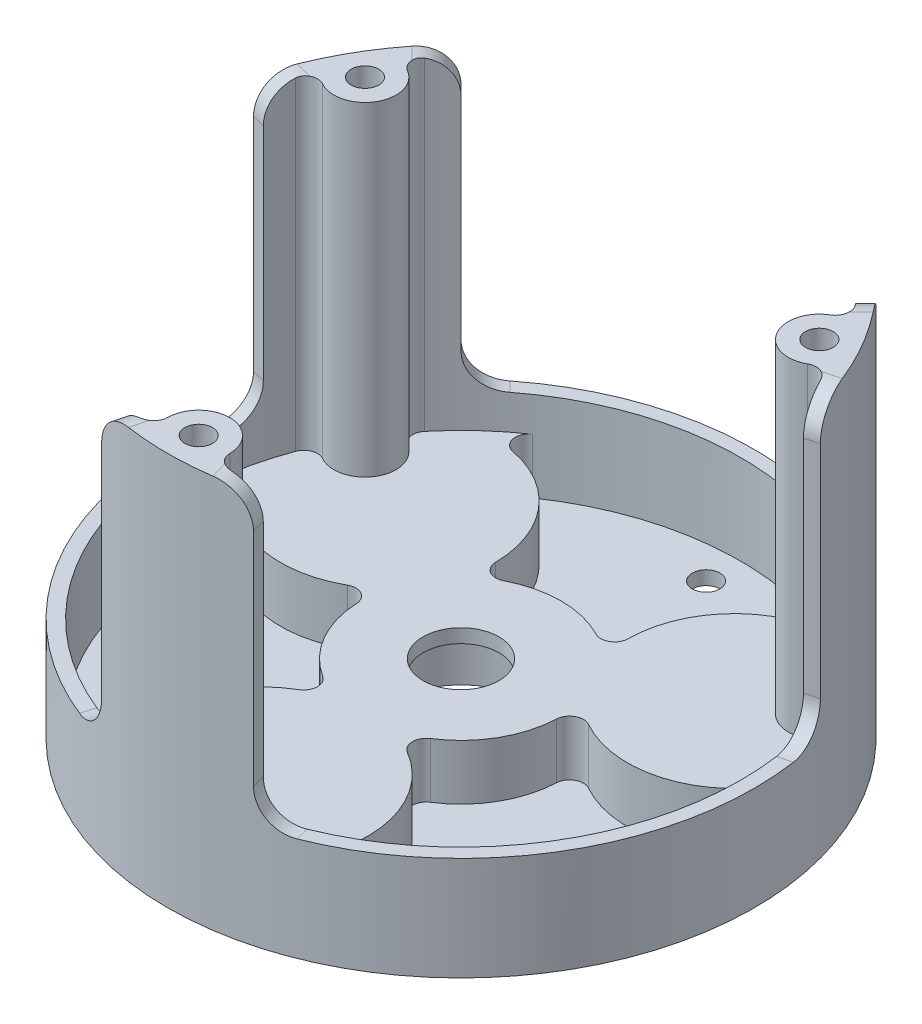
SolidWorks part; units mm, degrees
ref_plane "Front Plane" through (0, 0, 0) normal (0, 0, 1) x (1, 0, 0)
ref_plane "Top Plane" through (0, 0, 0) normal (0, 1, 0) x (1, 0, 0)
ref_plane "Right Plane" through (0, 0, 0) normal (1, 0, 0) x (0, 0, -1)
sketch "Sketch1" plane through (0, 0, 0) normal (0, 1, 0) x (1, 0, 0)
  circle A1 centre (0, 0) radius 42.5
  dimension "D2" = 85
extrude "Boss-Extrude1" add sketch "Sketch1" along normal mid plane 2
sketch "Sketch7" plane through (0, 0, 0) normal (0, 1, 0) x (1, 0, 0)
  circle A0 centre (0, 0) radius 42.5 construction
  arc A1 (-9.2002, -41.4922) -> (9.2002, -41.4922) centre (0, 0) ccw
  arc A3 (-40.5334, 12.7785) -> (-14.0359, 3.6391) centre (-25.1147, 14.5) ccw
  arc A4 (31.3332, 28.7137) -> (10.1695, 10.3359) centre (25.1147, 14.5) ccw
  arc A5 (9.2002, -41.4922) -> (3.8664, -13.975) centre (0, -29) ccw
  arc A6 (-10.1695, 10.3359) -> (-31.3332, 28.7137) centre (-25.1147, 14.5) ccw
  arc A8 (-31.3332, 28.7137) -> (-40.5334, 12.7785) centre (0, 0) ccw
  arc A9 (-14.0359, 3.6391) -> (-3.8664, -13.975) centre (0, 0) ccw
  arc A11 (40.5334, 12.7785) -> (31.3332, 28.7137) centre (0, 0) ccw
  arc A12 (14.0359, 3.6391) -> (40.5334, 12.7785) centre (25.1147, 14.5) ccw
  arc A15 (-3.8664, -13.975) -> (-9.2002, -41.4922) centre (0, -29) ccw
  arc A35 (10.1695, 10.3359) -> (-10.1695, 10.3359) centre (0, 0) ccw
  arc A37 (3.8664, -13.975) -> (14.0359, 3.6391) centre (0, 0) ccw
extrude "Boss-Extrude2" add sketch "Sketch7" along normal blind 9
sketch "Sketch8" plane through (0, 1, 0) normal (0, 1, 0) x (1, 0, 0)
  circle A1 centre (0, 0) radius 42.5
  circle A2 centre (0, 0) radius 40.5
  dimension "D1" = 2
extrude "Boss-Extrude3" add sketch "Sketch8" along normal blind 55
sketch "Sketch11" plane through (0, 9, 0) normal (0, 1, 0) x (1, 0, 0)
  circle A0 centre (-25.1147, 14.5) radius 5
  circle A1 centre (0, -29) radius 5
  circle A2 centre (25.1147, 14.5) radius 5
  dimension "D1" = 10
extrude "Cut-Extrude4" cut sketch "Sketch11" against normal blind 10 from offset 2 offset against normal yes
sketch "Sketch3" plane through (0, -1, 0) normal (0, -1, 0) x (1, 0, 0)
  circle A0 centre (0, 0) radius 9.5
  dimension "D1" = 19
extrude "Cut-Extrude2" cut sketch "Sketch3" against normal blind 8
sketch "Sketch14" plane through (0, 1, 0) normal (0, 1, 0) x (1, 0, 0)
  line L0 (0, 0) -> (0, 40.5) construction
  arc A0 (27.3728, 29.8493) -> (-27.3728, 29.8493) centre (0, 0) ccw construction
  circle A1 centre (0, 35.5) radius 2
  circle A2 centre (30.7439, -17.75) radius 2
  circle A3 centre (-30.7439, -17.75) radius 2
  point P15 (0, 0)
  dimension "D2" = 4
  dimension "D3" = 3
  dimension "D1" = 5
extrude "Cut-Extrude5" cut sketch "Sketch14" against normal through all
sketch "Sketch16" plane through (0, 7, 0) normal (0, -1, 0) x (1, 0, 0)
  circle A0 centre (0, 0) radius 5.5
  dimension "D1" = 11
extrude "Cut-Extrude7" cut sketch "Sketch16" against normal through all
fillet "Fillet4" radius 2 12 edges at (-39.5366, 5, -8.7809) (-27.3728, 5, -29.8493) (27.3728, 5, -29.8493) (39.5366, 5, -8.7809) (-14.0359, 5, -3.6391) (-10.1695, 5, -10.3359) (14.0359, 5, -3.6391) (10.1695, 5, -10.3359) (-3.8664, 5, 13.975) (3.8664, 5, 13.975) (-12.1639, 5, 38.6302) (12.1639, 5, 38.6302)
sketch "Sketch17" plane through (0, 56, 0) normal (0, 1, 0) x (1, 0, 0)
  line L0 (0, 0) -> (30.052, 30.052)
  line L1 (0, 0) -> (0, 42.5) construction
  line L2 (0, 0) -> (-30.052, 30.052)
  line L3 (0, 0) -> (41.0518, 10.9998)
  line L4 (0, 0) -> (10.9998, -41.0518)
  line L5 (0, 0) -> (-10.9998, -41.0518)
  line L6 (0, 0) -> (-41.0518, 10.9998)
  circle A0 centre (0, 0) radius 42.5 construction
  arc A1 (30.052, 30.052) -> (-30.052, 30.052) centre (0, 0) ccw
  arc A2 (10.9998, -41.0518) -> (41.0518, 10.9998) centre (0, 0) ccw
  arc A3 (-41.0518, 10.9998) -> (-10.9998, -41.0518) centre (0, 0) ccw
  point P14 (0, 0)
  circle M3 centre (0, 0) radius 42.5
  circle M4 centre (0, 0) radius 40.5
  dimension "D1" = 45
  dimension "D3" = 45
  dimension "D2" = 3
extrude "Cut-Extrude8" cut sketch "Sketch17" against normal offset from surface (42 mm away) 15 contours L5 L6 M4 | L1 L0 M4 | L3 L4 M4 | L6 L5 M4 M3 | L4 L3 M4 M3 | L0 A1 L2 region at (10.0689, 56, -24.3085) region at (21.0518, 56, 12.1543) region at (-21.0518, 56, 12.1543) region at (40.2441, 56, -10.1507) region at (-11.3313, 56, 39.9278) up to face at (0, -1, -33.5)
sketch "Sketch18" plane through (0, 9, 0) normal (0, 1, 0) x (1, 0, 0)
  line L0 (0, 0) -> (0, -42.5) construction
  arc A0 (-10.9998, -41.0518) -> (10.9998, -41.0518) centre (0, 0) ccw construction
  circle A1 centre (0, -38) radius 2
  circle A2 centre (0, -38) radius 4.5
  circle A3 centre (-32.909, 19) radius 4.5
  circle A4 centre (-32.909, 19) radius 2
  circle A5 centre (32.909, 19) radius 4.5
  circle A6 centre (32.909, 19) radius 2
  point P18 (0, 0)
  arc M5 (-22.9749, 33.3527) -> (-40.3718, 3.2204) centre (0, 0) ccw
  arc M13 (-17.3969, -36.5732) -> (17.3969, -36.5732) centre (0, 0) ccw
  arc M21 (40.3718, 3.2204) -> (22.9749, 33.3527) centre (0, 0) ccw
  dimension "D1" = 4
  dimension "D2" = 38
  dimension "D3" = 3
extrude "Boss-Extrude4" add sketch "Sketch18" along normal up to surface (47 mm away) contours A3 A4 M5 | A5 A6 M21 | A2 L0 A1 M13 | L0 A2 A1 M13 region at (2.351, 9, 37.1009) region at (-2.351, 9, 37.1009) region at (-31.8121, 9, -14.763) region at (34.9672, 9, -20.1883) up to face at (-35.3277, 56, -20.3965)
fillet "Fillet5" radius 2 6 edges at (-3.8584, 32.5, 40.3158) (3.8584, 32.5, 40.3158) (32.9853, 32.5, -23.4994) (36.8437, 32.5, -16.8164) (-32.9853, 32.5, -23.4994) (-36.8437, 32.5, -16.8164)
fillet "Fillet6" radius 5 6 edges at (29.3449, 14, -29.3449) (40.0859, 14, -10.741) (10.741, 14, 40.0859) (-10.741, 14, 40.0859) (-29.3449, 14, -29.3449) (-40.0859, 14, -10.741)
fillet "Fillet7" radius 5 6 edges at (29.3449, 56, -29.3449) (40.0859, 56, -10.741) (-29.3449, 56, -29.3449) (-40.0859, 56, -10.741) (-10.741, 56, 40.0859) (10.741, 56, 40.0859)
